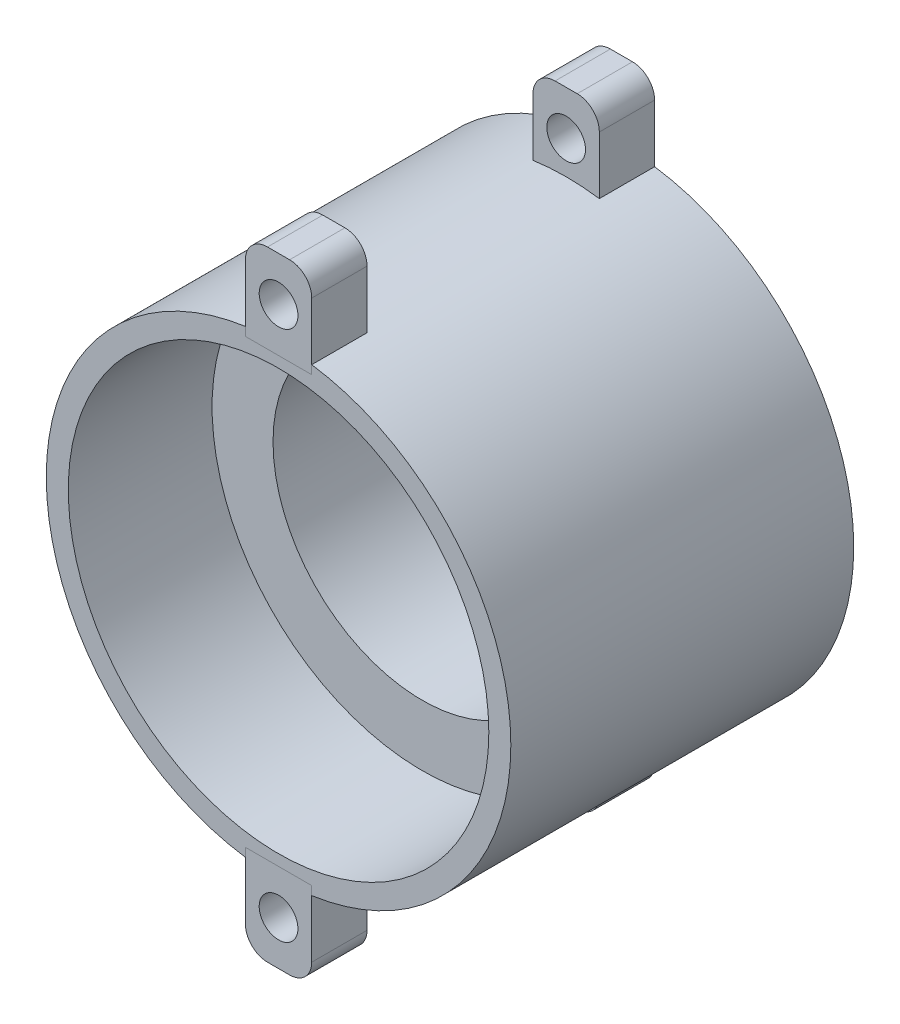
SolidWorks part; units mm, degrees
ref_plane "Front Plane" through (0, 0, 0) normal (0, 0, 1) x (1, 0, 0)
ref_plane "Top Plane" through (0, 0, 0) normal (0, 1, 0) x (1, 0, 0)
ref_plane "Right Plane" through (0, 0, 0) normal (1, 0, 0) x (0, 0, -1)
sketch "Sketch1" plane through (0, 0, 0) normal (0, 0, 1) x (1, 0, 0)
  circle A0 centre (0, 0) radius 13.5
  circle A1 centre (0, 0) radius 19.01
extrude "Boss-Extrude1" add sketch "Sketch1" along normal blind 18
sketch "Sketch2" plane through (0, 0, 18) normal (0, 0, 1) x (1, 0, 0)
  circle A0 centre (0, 0) radius 21
  circle A1 centre (0, 0) radius 19.01
extrude "Boss-Extrude2" add sketch "Sketch2" along normal blind 13 and the other way blind 18
sketch "Sketch3" plane through (0, 0, 0) normal (0, 0, -1) x (-1, 0, 0)
  line L0 (12.8914, 5.46) -> (17.4939, 7.4137)
  line L1 (15.5403, 12.0162) -> (10.9378, 10.0625)
  line L2 (15.5403, 12.0162) -> (19.4476, 2.8111)
  line L3 (19.4476, 2.8111) -> (14.8451, 0.8575)
  line L4 (10.9378, 10.0625) -> (14.8451, 0.8575)
  point P2 (12.8914, 5.46)
  point P6 (17.4939, 7.4137)
  dimension "D1" = 14
  dimension "D2" = 5.46
extrude "Cut-Extrude1" cut sketch "Sketch3" against normal offset from surface (13 mm away) 5 contours L1 L4 L3 L2 up to face at (19.01, 0, 18)
mirror "Mirror1" about plane through (0, 0, 0) normal (0, 1, 0) of "Cut-Extrude1"
mirror "Mirror2" about plane through (0, 0, 0) normal (1, 0, 0) of "Mirror1"
sketch "Sketch4" plane through (0, 0, 0) normal (0, 0, -1) x (-1, 0, 0)
  line L1 (-3, 28) -> (3, 28)
  line L2 (-3, 28) -> (-3, 20)
  line L3 (-3, 20) -> (3, 20)
  line L4 (3, 28) -> (3, 20)
  circle A0 centre (0, 24) radius 1.75
  point P4 (0, 20)
  dimension "D1" = 4
  dimension "D2" = 20
extrude "Boss-Extrude3" add sketch "Sketch4" along normal blind 0.0001 and the other way blind 5
fillet "Fillet1" radius 2 2 edges at (3, 28, 2.5) (-3, 28, 2.5)
mirror "Mirror5" about plane through (0, 0, 0) normal (0, 1, 0) of "Fillet1", "Boss-Extrude3"
sketch "Sketch7" plane through (0, 0, 31) normal (0, 0, 1) x (1, 0, 0)
  line L1 (-3, 28) -> (3, 28)
  line L2 (-3, 28) -> (-3, 20)
  line L3 (-3, 20) -> (3, 20)
  line L4 (3, 28) -> (3, 20)
  circle A0 centre (0, 24) radius 1.75
  point P4 (0, 20)
  dimension "D1" = 20
  dimension "D2" = 4
extrude "Boss-Extrude6" add sketch "Sketch7" along normal blind 0.0001 and the other way blind 5
mirror "Mirror6" about plane through (0, 0, 0) normal (0, 1, 0) of "Boss-Extrude6"
fillet "Fillet2" radius 2 4 edges at (-3, 28, 28.5) (3, 28, 28.5) (3, -28, 28.5) (-3, -28, 28.5)
